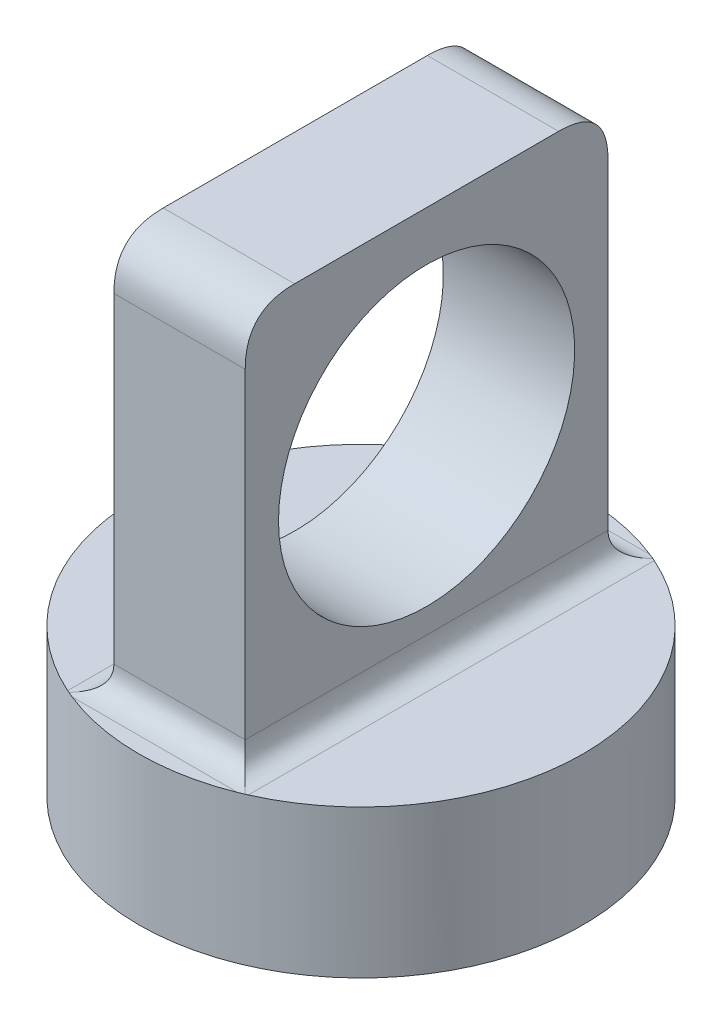
SolidWorks part; units mm, degrees
ref_plane "Front Plane" through (0, 0, 0) normal (0, 0, 1) x (1, 0, 0)
ref_plane "Top Plane" through (0, 0, 0) normal (0, 1, 0) x (1, 0, 0)
ref_plane "Right Plane" through (0, 0, 0) normal (1, 0, 0) x (0, 0, -1)
sketch "Sketch1" plane through (0, 0, 0) normal (0, 1, 0) x (1, 0, 0)
  circle A0 centre (0, 0) radius 114.3
  dimension "D1" = 228.6
extrude "Boss-Extrude1" add sketch "Sketch1" along normal blind 76.2
sketch "Sketch2" plane through (0, 0, 0) normal (0, -1, 0) x (-1, 0, 0)
  circle A0 centre (0, 0) radius 88.9
sketch "Sketch3" plane through (0, 76.2, 0) normal (0, 1, 0) x (1, 0, 0)
  line L0 (-0.0261, 0) -> (-0.0261, 130.3975) construction
  line L1 (-33.8081, 93.345) -> (33.7559, 93.345)
  line L2 (-33.8081, 93.345) -> (-33.8081, -93.345)
  line L3 (-33.8081, -93.345) -> (33.7559, -93.345)
  line L4 (33.7559, 93.345) -> (33.7559, -93.345)
  line L6 (0, 0) -> (148.4029, 0) construction
  dimension "D1" = 67.564
  dimension "D2" = 186.69
extrude "Boss-Extrude3" add sketch "Sketch3" along normal blind 203.2
sketch "Sketch4" plane through (-33.8081, 0, 0) normal (-1, 0, 0) x (0, 0, 1)
  line L0 (93.345, 279.4) -> (-93.345, 76.2) construction
  line L1 (-93.345, 279.4) -> (93.345, 76.2) construction
  circle A0 centre (0, 177.8) radius 76.2
  dimension "D1" = 152.4
extrude "Cut-Extrude1" cut sketch "Sketch4" against normal blind 127
fillet "Fillet1" radius 25.4 2 edges at (-0.0261, 279.4, 93.345) (-0.0261, 279.4, -93.345) conic rho 0.5
fillet "Fillet2" radius 12.7 4 edges at (-0.0261, 76.2, 93.345) (-0.0261, 76.2, -93.345) (-33.8081, 76.2, 0) (33.7559, 76.2, 0) conic rho 0.5
extrude "Cut-Extrude2" cut sketch "Sketch2" against normal blind 38.1
